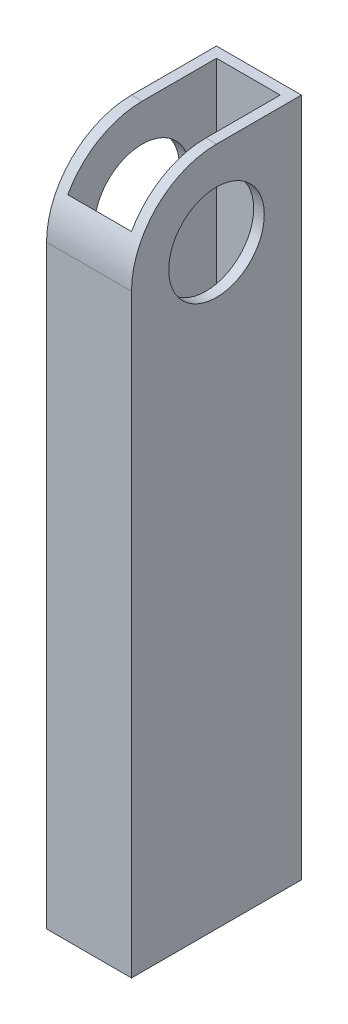
SolidWorks part; units mm, degrees
material "1060 Alloy"
ref_plane "Front Plane" through (0, 0, 0) normal (0, 0, 1) x (1, 0, 0)
ref_plane "Top Plane" through (0, 0, 0) normal (0, 1, 0) x (1, 0, 0)
ref_plane "Right Plane" through (0, 0, 0) normal (1, 0, 0) x (0, 0, -1)
sketch "Sketch1" plane through (0, 0, 0) normal (0, 1, 0) x (1, 0, 0)
  line L0 (-12.7, -25.4) -> (12.7, 25.4) construction
  line L1 (-12.7, -25.4) -> (12.7, -25.4)
  line L2 (-12.7, -25.4) -> (-12.7, 25.4)
  line L3 (-12.7, 25.4) -> (12.7, 25.4)
  line L4 (12.7, -25.4) -> (12.7, 25.4)
  point P0 (0, 0)
  point P7 (0, 0)
  dimension "1" = 25.4
  dimension "D2" = 50.8
extrude "Extrude-Thin1" add sketch "Sketch1" along normal blind 203.2 thin thin type one direction reverse wall 3.175
sketch "Sketch2" plane through (12.7, 0, 0) normal (1, 0, 0) x (0, 0, -1)
  line L0 (-25.4, 203.2) -> (25.4, 203.2) construction
  circle A0 centre (0, 177.8) radius 14.2875
  point P5 (0, 203.2)
  dimension "D1" = 28.575
  dimension "D2" = 25.4
extrude "Cut-Extrude1" cut sketch "Sketch2" against normal through all
sketch "Sketch3" [suppressed] plane through (0, 0, -12.7) normal (0, 0, -1) x (-1, 0, 0)
  line L0 (-12.7, 0) -> (12.7, 0) construction
  circle A0 centre (0, 12.7) radius 9.525
  dimension "D1" = 19.05
  dimension "D2" = 19.05
extrude "Cut-Extrude2" [suppressed] cut sketch "Sketch3" against normal through all
sketch "Sketch4" plane through (12.7, 0, 0) normal (1, 0, 0) x (0, 0, -1)
  line L1 (-25.4, 203.2) -> (-25.4, 0) construction
  line L2 (-25.4, 203.2) -> (0, 203.2)
  line L6 (-25.4, 190.5) -> (-25.4, 203.2)
  line L7 (-25.4, 203.2) -> (25.4, 203.2) construction
  line L10 (-25.4, 177.8) -> (-25.4, 190.5)
  arc A2 (0, 203.2) -> (-25.4, 177.8) centre (0, 177.8) ccw
extrude "Cut-Extrude3" cut sketch "Sketch4" against normal through all
